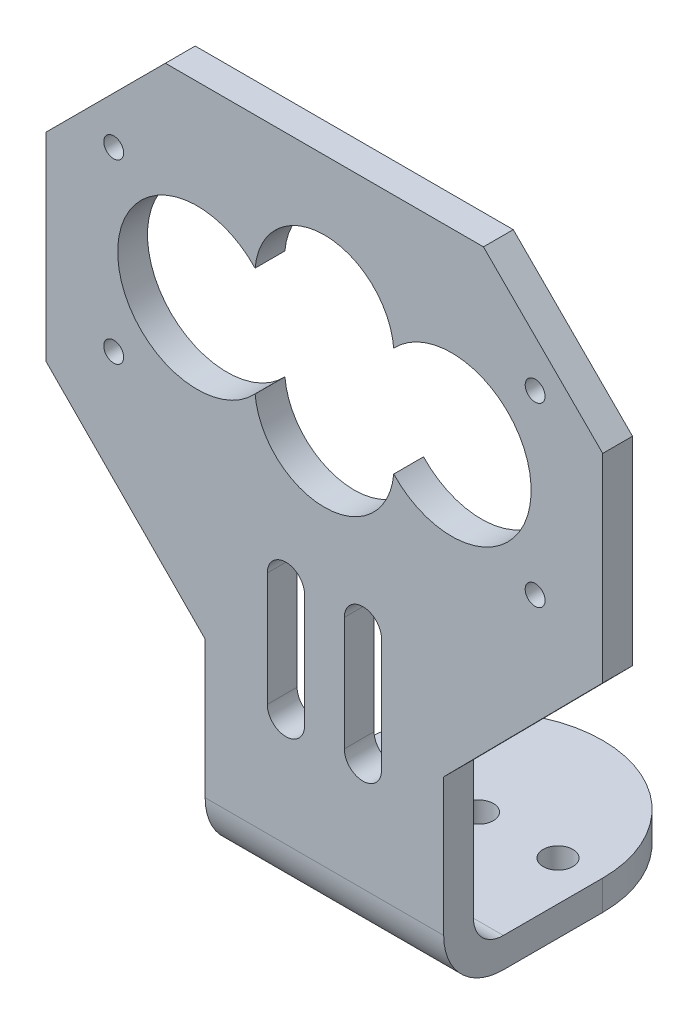
SolidWorks part; units mm, degrees
material "Acrylic (Medium-high impact)"
ref_plane "Front Plane" through (0, 0, 0) normal (0, 0, 1) x (1, 0, 0)
ref_plane "Top Plane" through (0, 0, 0) normal (0, 1, 0) x (1, 0, 0)
ref_plane "Right Plane" through (0, 0, 0) normal (1, 0, 0) x (0, 0, -1)
sketch "Sketch1" plane through (0, 0, 0) normal (0, 0, 1) x (1, 0, 0)
  line L0 (10.5357, 60.5446) -> (-5.4643, 44.3661)
  line L2 (-45.4643, 80.5446) -> (-45.4643, 60.5446)
  line L4 (10.5357, 80.5446) -> (10.5357, 60.5446)
  line L5 (-33.4643, 92.5446) -> (-1.4643, 92.5446)
  line L9 (-45.4643, 60.5446) -> (-29.4643, 44.3661)
  line L10 (-22.4956, 73.7179) -> (-22.2643, 73.7179)
  line L11 (-29.4643, 24.5446) -> (-5.4643, 24.5446)
  line L12 (-29.4643, 24.5446) -> (-29.4643, 44.3661)
  line L14 (-5.4643, 24.5446) -> (-5.4643, 44.3661)
  line L15 (-13.5909, 53.2585) -> (-13.5909, 41.8039) construction
  line L16 (-11.7174, 53.2585) -> (-11.7174, 41.8039)
  line L17 (-15.4643, 53.2585) -> (-15.4643, 41.8039)
  line L18 (10.5357, 80.5446) -> (-1.4643, 92.5446)
  line L19 (-45.4643, 80.5446) -> (-33.4643, 92.5446)
  line L21 (-21.3377, 53.2585) -> (-21.3377, 41.8039) construction
  line L22 (-23.2111, 53.2585) -> (-23.2111, 41.8039)
  line L23 (-19.4643, 53.2585) -> (-19.4643, 41.8039)
  arc A0 (-10.4913, 79.1992) -> (-24.4373, 79.1992) centre (-17.4643, 78.5847) ccw
  arc A1 (-24.4373, 79.1992) -> (-24.4373, 68.2365) centre (-30.2643, 73.7179) ccw
  circle A3 centre (3.7357, 82.6179) radius 1
  circle A4 centre (-38.6643, 64.8179) radius 1
  circle A5 centre (-38.6643, 82.6179) radius 1
  circle A6 centre (3.7357, 64.8179) radius 1
  arc A7 (-10.4913, 68.2365) -> (-24.4373, 68.2365) centre (-17.4643, 68.851) cw
  arc A8 (-10.4913, 68.2365) -> (-10.4913, 79.1992) centre (-4.6643, 73.7179) ccw
  arc A10 (-11.7174, 53.2585) -> (-15.4643, 53.2585) centre (-13.5909, 53.2585) ccw
  arc A11 (-22.4956, 73.7179) -> (-22.2675, 73.4926) centre (-17.4643, 78.5847) ccw
  arc A12 (-22.4956, 73.7179) -> (-22.2675, 73.9431) centre (-17.4643, 68.851) cw
  arc A13 (-22.2675, 73.4926) -> (-22.2675, 73.9431) centre (-30.2643, 73.7179) ccw
  arc A14 (-15.4643, 41.8039) -> (-11.7174, 41.8039) centre (-13.5909, 41.8039) ccw
  arc A15 (-23.2111, 53.2585) -> (-19.4643, 53.2585) centre (-21.3377, 53.2585) cw
  arc A16 (-19.4643, 41.8039) -> (-23.2111, 41.8039) centre (-21.3377, 41.8039) cw
  point P4 (-17.4643, 82.9018)
  point P9 (-17.4643, 34.4554)
  point P36 (-13.5909, 47.5312)
  point P44 (-21.3377, 47.5312)
  dimension "D1" = 20
  dimension "D2" = 32
  dimension "D3" = 56
  dimension "D4" = 24
  dimension "D5" = 68
  dimension "D7" = 3.7469
extrude "Boss-Extrude1" add sketch "Sketch1" along normal blind 3 contours L19 L2 L9 L12 L11 L14 L0 L4 L18 L5 A14 L17 A10 L16 A8 A7 A1 A5 A4 A3 A6 L23 A16 L22 A15 region at (-17.4643, 60.6697, 0)
sketch "Sketch2" plane through (0, 0, 0) normal (0, 0, -1) x (-1, 0, 0)
  line L0 (29.4643, 24.5446) -> (29.4643, 44.3661) construction
  line L1 (5.4643, 24.5446) -> (29.4643, 24.5446)
  line L2 (5.4643, 24.5446) -> (5.4643, 27.5446)
  line L3 (5.4643, 27.5446) -> (29.4643, 27.5446)
  line L4 (29.4643, 24.5446) -> (29.4643, 27.5446)
extrude "Boss-Extrude2" add sketch "Sketch2" along normal blind 25
fillet "Fillet3" radius 12 2 edges at (-29.4643, 26.0446, -25) (-5.4643, 26.0446, -25)
sketch "Sketch3" plane through (0, 27.5446, 0) normal (0, 1, 0) x (1, 0, 0)
  line L0 (-29.4643, 0) -> (-5.4643, 0) construction
  circle A0 centre (-17.4643, 12.5) radius 1.5
  circle A1 centre (-25.4643, 12.5) radius 1.5
  circle A2 centre (-9.4643, 12.5) radius 1.5
  dimension "D1" = 8
  dimension "D2" = 8
  dimension "D3" = 12.5
extrude "Cut-Extrude1" cut sketch "Sketch3" against normal blind 25
fillet "Fillet5" radius 3 1 edges at (-17.4643, 27.5446, 0)
fillet "Fillet6" radius 6 1 edges at (-17.4643, 24.5446, 3)
